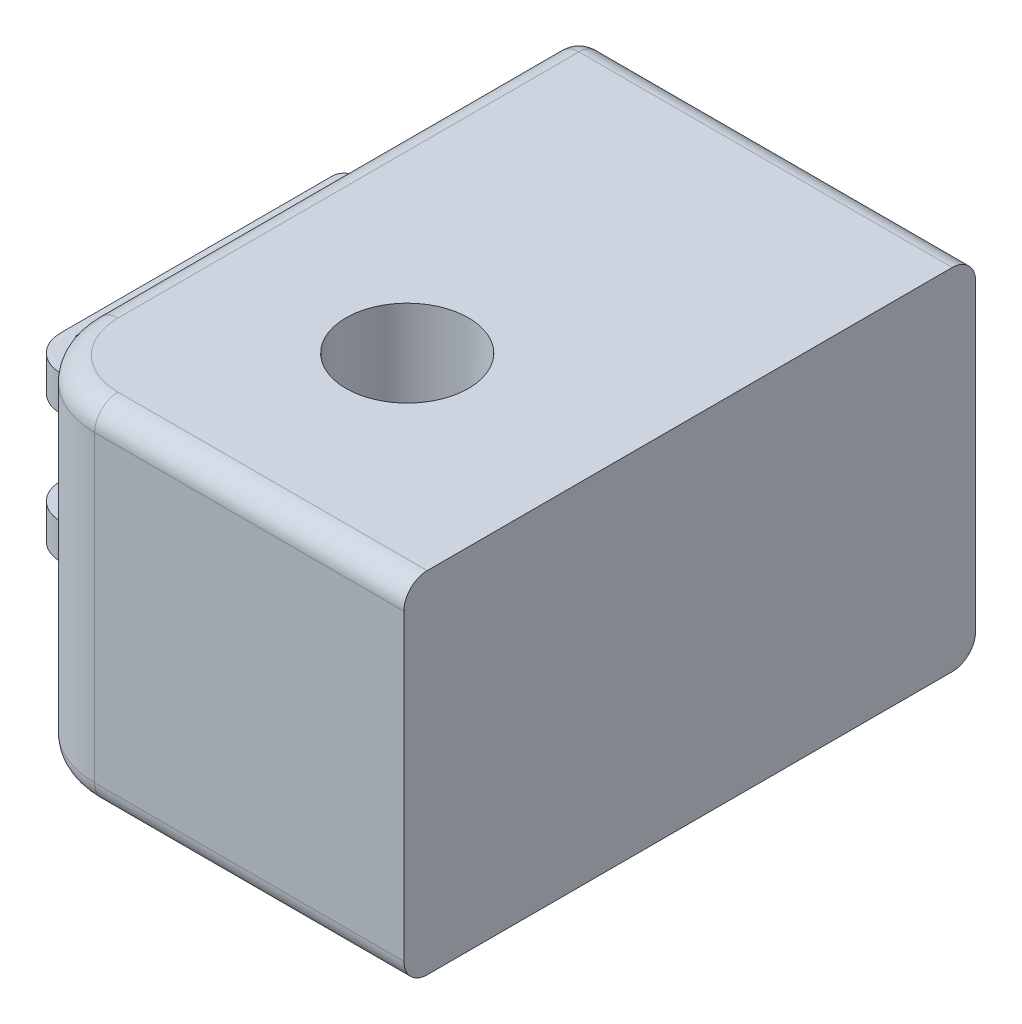
SolidWorks part; units mm, degrees
ref_plane "Front Plane" through (0, 0, 0) normal (0, 0, 1) x (1, 0, 0)
ref_plane "Top Plane" through (0, 0, 0) normal (0, 1, 0) x (1, 0, 0)
ref_plane "Right Plane" through (0, 0, 0) normal (1, 0, 0) x (0, 0, -1)
sketch "Sketch1" plane through (0, 0, 0) normal (0, 0, 1) x (1, 0, 0)
  line L1 (17, -15) -> (-17, -15)
  line L2 (17, -15) -> (17, 15)
  line L3 (17, 15) -> (-17, 15)
  line L4 (-17, -15) -> (-17, 15)
  dimension "D1" = 34
  dimension "D2" = 30
  dimension "D3" = 15
  dimension "D4" = 17
extrude "Boss-Extrude1" add sketch "Sketch1" along normal blind 49
sketch "Sketch2" plane through (0, 0, 0) normal (0, 0, -1) x (-1, 0, 0)
  line L0 (-17, -15) -> (-17, 15) construction
  line L1 (17, -15) -> (-17, -15) construction
  circle A4 centre (-12, 9) radius 2 construction
  circle A5 centre (-12, -9) radius 2 construction
  circle A6 centre (12, -9) radius 2 construction
  circle A7 centre (12, 9) radius 2 construction
  circle A8 centre (12, -9) radius 2.1
  circle A9 centre (12, 9) radius 2.1
  circle A10 centre (-12, -9) radius 2.1
  circle A11 centre (-12, 9) radius 2.1
  dimension "D1" = 4
  dimension "D2" = 5
  dimension "D3" = 29
  dimension "D4" = 6
  dimension "D5" = 24
  dimension "D6" = 0.1
extrude "Cut-Extrude1" cut sketch "Sketch2" against normal blind 6
sketch "Sketch5" plane through (0, -15, 0) normal (0, -1, 0) x (1, 0, 0)
  line L0 (17, 49) -> (17, 0) construction
  line L2 (-17, 49) -> (17, 49) construction
  circle A1 centre (0, 31.7136) radius 11 construction
  circle A3 centre (0, 31.7136) radius 11.15
  dimension "D1" = 22
  dimension "D2" = 17
  dimension "D3" = 17.2864
  dimension "D4" = 0.15
extrude "Cut-Extrude2" cut sketch "Sketch5" against normal blind 12.5
sketch "Sketch6" plane through (0, 15, 0) normal (0, 1, 0) x (1, 0, 0)
  circle A1 centre (0, -31.7136) radius 5.1 construction
  circle A2 centre (0, -31.7136) radius 5.25
  dimension "D1" = 10.2
  dimension "D4" = 0.15
extrude "Cut-Extrude3" cut sketch "Sketch6" against normal blind 17.5
sketch "Sketch7" plane through (0, -2.5, 0) normal (0, -1, 0) x (1, 0, 0)
  circle A4 centre (7.9785, 31.127) radius 1.75 construction
  circle A5 centre (-0.5866, 39.6921) radius 1.75 construction
  circle A6 centre (-7.9785, 31.127) radius 1.75 construction
  circle A7 centre (0.5866, 23.7351) radius 1.75 construction
  circle A8 centre (-7.9785, 31.127) radius 2.1
  circle A9 centre (-0.5866, 39.6921) radius 2.1
  circle A10 centre (7.9785, 31.127) radius 2.1
  circle A11 centre (0.5866, 23.7351) radius 2.1
  circle A12 centre (0, 31.7136) radius 5.25 construction
  dimension "D2" = 4.2
  dimension "D3" = 0.5866
  dimension "D4" = 7.9785
  dimension "D5" = 0.5866
  dimension "D6" = 7.9785
  dimension "D7" = 0.5866
  dimension "D8" = 7.9785
  dimension "D9" = 0.5866
  dimension "D10" = 7.9785
  dimension "D1" = 0.35
extrude "Cut-Extrude4" cut sketch "Sketch7" against normal blind 6
chamfer "Chamfer1" distance 1 angle 45 4 edges at (7.9785, -2.5, 29.027) (-0.5866, -2.5, 37.5921) (-7.9785, -2.5, 29.027) (0.5866, -2.5, 21.6351)
chamfer "Chamfer2" distance 1 angle 45 4 edges at (9.9, -9, 0) (-14.1, -9, 0) (-14.1, 9, 0) (9.9, 9, 0)
fillet "Fillet1" radius 7.5 1 edges at (-17, 0, 49)
fillet "Fillet2" radius 2 9 edges at (-17, 15, 20.75) (3.75, 15, 49) (3.75, -15, 49) (-17, -15, 20.75) (0, -15, 0) (-17, 0, 0) (0, 15, 0) (-14.8033, 15, 46.8033) (-14.8033, -15, 46.8033)
sketch "Sketch8" plane through (17, 0, 0) normal (1, 0, 0) x (0, 0, -1)
  line L1 (-42, 9) -> (-7, 9) construction
  line L2 (-42, 9) -> (-42, -9) construction
  line L3 (-42, -9) -> (-7, -9) construction
  line L4 (-7, 9) -> (-7, -9) construction
  line L5 (-42, 9) -> (-7, -9) construction
  line L6 (-42, -9) -> (-7, 9) construction
  line L7 (-47, 15) -> (-2, 15) construction
  circle A0 centre (-42, 9) radius 2.075
  circle A1 centre (-7, 9) radius 2.075
  circle A2 centre (-7, -9) radius 2.075
  circle A3 centre (-42, -9) radius 2.075
  point P0 (-24.5, 0)
  point P14 (-24.5, 15)
  dimension "D1" = 4.15
  dimension "D2" = 35
  dimension "D3" = 18
extrude "Cut-Extrude5" [suppressed] cut sketch "Sketch8" against normal blind 6.5
chamfer "Chamfer3" [suppressed] distance 1.5 angle 45
sketch "Sketch9" plane through (0, 0, 0) normal (0, 1, 0) x (1, 0, 0)
  line L0 (-17, -40.0491) -> (-24.3539, -40.0491)
  line L1 (-17, -2) -> (-17, -41.5) construction
  line L2 (-24.3539, -40.0491) -> (-24.3539, -12.7622)
  line L3 (-24.3539, -12.7622) -> (-17, -12.7622)
  line L4 (-17, -12.7622) -> (-17, -40.0491)
  line L5 (-20.6, -35) -> (-20.6, -19)
  circle A1 centre (-20.6, -35) radius 1.625
  circle A2 centre (-20.6, -19) radius 1.625
  dimension "D3" = 3.25
  dimension "D1" = 3.6
  dimension "D2" = 16
extrude "Boss-Extrude2" add sketch "Sketch9" along normal blind 3 from offset 4 contours L4 L3 L2 L0 A2 A1 region at (-20.6839, 0, 26.3521)
mirror "Mirror1" about plane through (0, 0, 0) normal (0, 1, 0) of "Boss-Extrude2"
fillet "Fillet3" radius 3 2 edges at (-24.3539, 5.5, 40.0491) (-24.3539, -5.5, 40.0491)
fillet "Fillet4" radius 1 4 edges at (-24.3539, 5.5, 12.7622) (-17, 5.5, 12.7622) (-17, -5.5, 12.7622) (-24.3539, -5.5, 12.7622)
sketch "Sketch10" plane through (0, 7, 0) normal (0, 1, 0) x (1, 0, 0)
  line L1 (-17.725, -20.6599) -> (-17.725, -17.3401)
  line L2 (-17.725, -17.3401) -> (-20.6, -15.6802)
  line L3 (-20.6, -15.6802) -> (-23.475, -17.3401)
  line L4 (-23.475, -17.3401) -> (-23.475, -20.6599)
  line L5 (-23.475, -20.6599) -> (-20.6, -22.3198)
  line L6 (-20.6, -22.3198) -> (-17.725, -20.6599)
  line L7 (-17.725, -36.6599) -> (-17.725, -33.3401)
  line L8 (-17.725, -33.3401) -> (-20.6, -31.6802)
  line L9 (-20.6, -31.6802) -> (-23.475, -33.3401)
  line L10 (-23.475, -33.3401) -> (-23.475, -36.6599)
  line L11 (-23.475, -36.6599) -> (-20.6, -38.3198)
  line L12 (-20.6, -38.3198) -> (-17.725, -36.6599)
  circle A0 centre (-20.6, -19) radius 2.875 construction
  circle A1 centre (-20.6, -35) radius 2.875 construction
  dimension "D1" = 5.75
extrude "Cut-Extrude6" cut sketch "Sketch10" against normal blind 2
ref_plane "Plane1" through (0, 0, 18.18) normal (0, 0, -1) x (-1, 0, 0)
sketch "Sketch13" plane through (0, -15, 0) normal (0, -1, 0) x (1, 0, 0)
  line L0 (-14.3, 18.18) -> (14.3, 18.18) construction
  line L1 (-9, 25.73) -> (11, 25.73) construction
  line L2 (-9, 25.73) -> (-9, 10.63) construction
  line L3 (-9, 10.63) -> (11, 10.63) construction
  line L4 (11, 25.73) -> (11, 10.63) construction
  line L5 (-15, 2) -> (17, 2) construction
  circle A0 centre (-9, 25.73) radius 2.05
  circle A1 centre (11, 25.73) radius 2.05
  circle A2 centre (-9, 10.63) radius 2.05
  circle A3 centre (11, 10.63) radius 2.05
  point P10 (11, 18.18)
  point P15 (1, 2)
  point P16 (1, 10.63)
  dimension "D1" = 4.1
  dimension "D2" = 5.5
  dimension "D3" = 20
extrude "Cut-Extrude7" [suppressed] cut sketch "Sketch13" against normal through all
chamfer "Chamfer4" [suppressed] distance 1 angle 45
